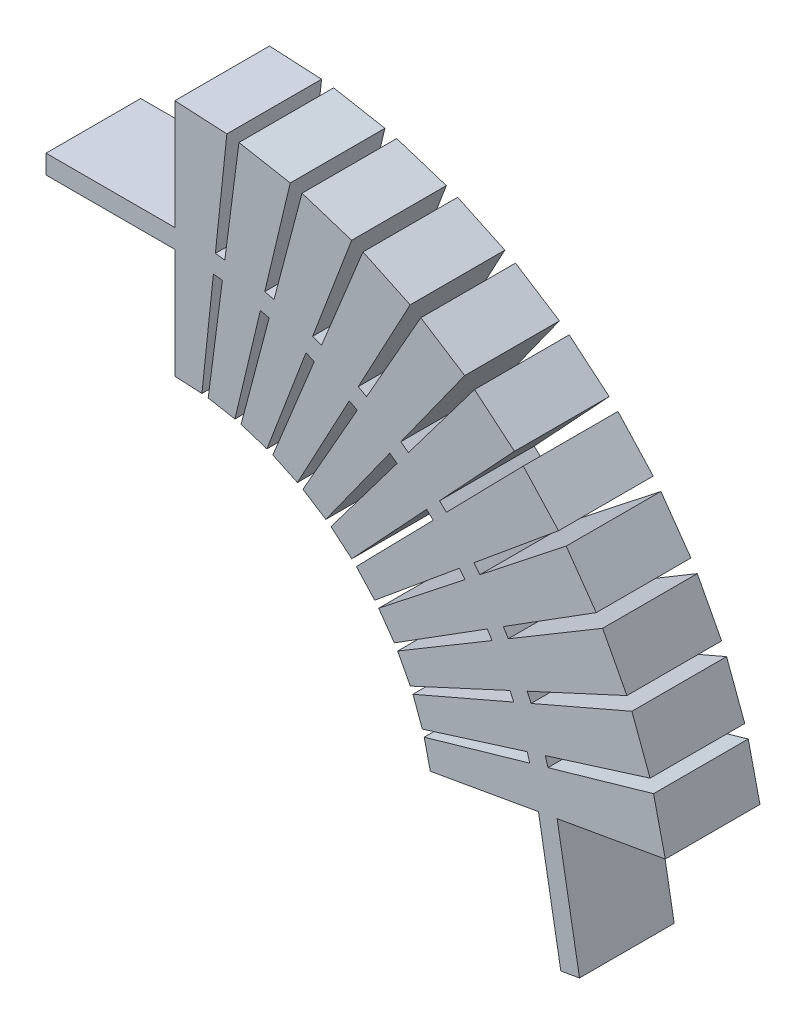
SolidWorks part; units mm, degrees
ref_plane "Ebene vorne" through (0, 0, 0) normal (0, 0, 1) x (1, 0, 0)
ref_plane "Ebene oben" through (0, 0, 0) normal (0, 1, 0) x (1, 0, 0)
ref_plane "Ebene rechts" through (0, 0, 0) normal (1, 0, 0) x (0, 0, -1)
sketch "Skizze1" plane through (0, 0, 0) normal (0, 0, 1) x (1, 0, 0)
  line L0 (0, 40) -> (0, 0) construction
  line L1 (0, 0) -> (39.3923, 6.9459) construction
  line L2 (0, 41) -> (0, 40)
  line L3 (40.3771, 7.1196) -> (39.3923, 6.9459)
  arc A0 (0, 40) -> (39.3923, 6.9459) centre (0, 0) cw
  arc A1 (0, 41) -> (40.3771, 7.1196) centre (0, 0) cw
  dimension "D1" = 40
  dimension "D2" = 1
  dimension "D3" = 80
extrude "Aufsatz-Linear austragen1" add sketch "Skizze1" along normal mid plane 10
sketch "Skizze2" plane through (0, 0, 0) normal (0, 0, 1) x (1, 0, 0)
  line L0 (0, 41) -> (0, 52.6)
  line L1 (0, 52.6) -> (5.4982, 52.3119)
  line L2 (5.4982, 52.3119) -> (4.2857, 40.7754)
  line L3 (1.8606, 35.5018) -> (-2612.3549, -49846.7015) construction
  line L4 (0, 41) -> (4.2857, 40.7754)
  arc A0 (40.3771, 7.1196) -> (0, 41) centre (0, 0) ccw construction
  arc A1 (40.3771, 7.1196) -> (0, 41) centre (0, 0) ccw construction
  arc A2 (0, 41) -> (4.2857, 40.7754) centre (0, 0) cw
  point P7 (2.1458, 40.9438)
  point P9 (2.7491, 52.4559)
  point P11 (2.1428, 40.8877)
  dimension "D1" = 11.6
  dimension "D2" = 6
extrude "Aufsatz-Linear austragen2" add sketch "Skizze2" along normal mid plane 10 contours L0 A2 L2 L1 region at (2.4594, 46.9278, 0)
ref_axis "Achse1" through (0, 0, -5.5) along (0, 0, 1)
pattern_circular "Kreismuster1" count 11 every 7.4 about axis through (0, 0, -5.5) along (0, 0, 1) of "Aufsatz-Linear austragen2" reverse direction yes
sketch "Skizze4" plane through (0, 0, 0) normal (0, 0, 1) x (1, 0, 0)
  line L0 (0, 40) -> (0, 39)
  line L1 (39.3923, 6.9459) -> (38.4075, 6.7723)
  line L2 (39.3923, 6.9459) -> (51.8009, 9.1339) construction
  arc A0 (39.3923, 6.9459) -> (0, 40) centre (0, 0) ccw construction
  arc A1 (39.3923, 6.9459) -> (0, 40) centre (0, 0) ccw
  arc A2 (38.4075, 6.7723) -> (0, 39) centre (0, 0) ccw
  dimension "D1" = 1
extrude "Aufsatz-Linear austragen4" add sketch "Skizze4" along normal mid plane 10
sketch "Skizze3" plane through (0, 0, 0) normal (0, 0, 1) x (1, 0, 0)
  line L3 (5.4982, 52.3119) -> (4.2857, 40.7754) construction
  line L4 (5.4982, 52.3119) -> (4.2857, 40.7754) construction
  line L5 (0, 40) -> (49931.4767, -2576.7978) construction
  line L6 (-1.1289, 27.4592) -> (49930.3478, -2589.3386) construction
  line L7 (0, 40) -> (0, 27.4)
  line L8 (0, 52.6) -> (0, 39) construction
  line L9 (0, 27.4) -> (2.8641, 27.2499)
  line L10 (2.8641, 27.2499) -> (4.1811, 39.7809)
  line L15 (4.2857, 40.7754) -> (4.0766, 38.7864) construction
  line L16 (4.0766, 38.7864) -> (0, 0) construction
  line L17 (4.1811, 39.7809) -> (0, 40)
  line L18 (0, 52.6) -> (0, 39) construction
  arc A4 (5.2806, 40.6585) -> (4.2857, 40.7754) centre (0, 0) ccw construction
  arc A6 (5.2806, 40.6585) -> (4.2857, 40.7754) centre (0, 0) ccw construction
  circle A7 centre (0, 0) radius 39 construction
  circle A8 centre (0, 0) radius 41 construction
  circle A9 centre (0, 0) radius 40 construction
  point P0 (4.1811, 39.7809)
  point P8 (4.1811, 27.1809)
  point P10 (-1.3171, 27.469)
  point P11 (0, 40)
extrude "Aufsatz-Linear austragen3" add sketch "Skizze3" along normal mid plane 10 contours L17 L7 L9 L10
pattern_circular "Kreismuster4" count 11 every 7.4 about axis through (0, 0, -5.5) along (0, 0, 1) of "Aufsatz-Linear austragen3" reverse direction yes
sketch "Skizze5" plane through (0, 0, 0) normal (-1, 0, 0) x (0, 0, 1)
  line L0 (5, 52.6) -> (5, 27.4) construction
  line L1 (5, 41) -> (-5, 41)
  line L2 (5, 41) -> (5, 39)
  line L3 (5, 39) -> (-5, 39)
  line L4 (-5, 41) -> (-5, 39)
  line L5 (-5, 52.6) -> (-5, 27.4) construction
  line L6 (5, 52.6) -> (5, 27.4) construction
  line L7 (5, 40) -> (-49995, 40) construction
  point P12 (5, 40)
  dimension "D1" = 2
extrude "Aufsatz-Linear austragen5" add sketch "Skizze5" along normal blind 13.6
sketch "Skizze6" plane through (0, 0, 0) normal (0.1736, -0.9848, 0) x (0.9848, 0.1736, 0)
  line L0 (40, 5) -> (40, -49995) construction
  line L1 (27.4, 5) -> (52.6, 5) construction
  line L2 (27.4, -5) -> (52.6, -5) construction
  line L3 (41, 5) -> (39, 5)
  line L4 (41, 5) -> (41, -5)
  line L5 (41, -5) -> (39, -5)
  line L6 (39, 5) -> (39, -5)
  point P4 (40, 5)
  dimension "D1" = 2
extrude "Aufsatz-Linear austragen6" add sketch "Skizze6" along normal blind 13.6
